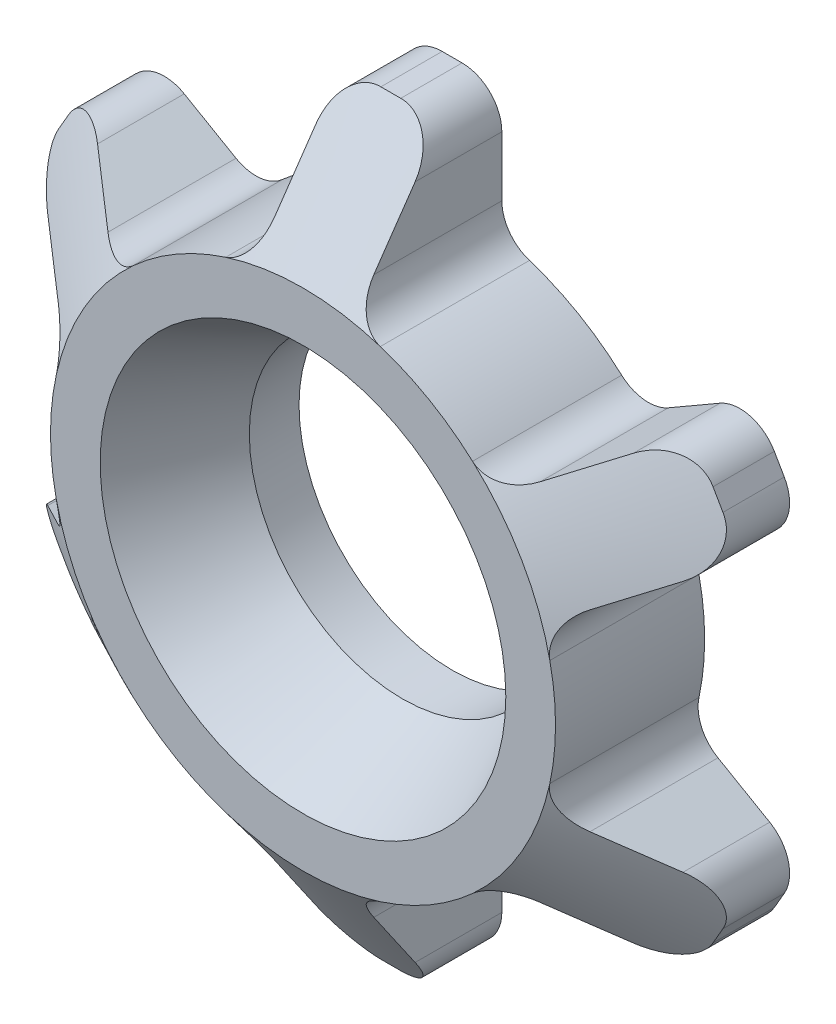
SolidWorks part; units mm, degrees
ref_plane "Front Plane" through (0, 0, 0) normal (0, 0, 1) x (1, 0, 0)
ref_plane "Top Plane" through (0, 0, 0) normal (0, 1, 0) x (1, 0, 0)
ref_plane "Right Plane" through (0, 0, 0) normal (1, 0, 0) x (0, 0, -1)
ref_axis "Axis1" through (0, 0, -0.7711) along (0, 0, 1)
sketch "Sketch1" plane through (0, 0, 0) normal (0, 0, 1) x (1, 0, 0)
  line L0 (0, 0) -> (0, 24.13)
  line L1 (-3.175, 24.13) -> (3.175, 24.13)
  line L2 (3.175, 24.13) -> (3.175, 15.8134)
  line L3 (-3.175, 24.13) -> (-3.175, 15.8134)
  circle A0 centre (0, 0) radius 9.779
  circle A1 centre (0, 0) radius 16.129
  point P9 (0, 24.13)
  dimension "D1" = 19.558
  dimension "D2" = 6.35
  dimension "D3" = 24.13
  dimension "D4" = 6.35
extrude "Boss-Extrude1" add sketch "Sketch1" along normal blind 9.525 contours A1 A0 | A1 L0 L1 L3 | A1 L2 L1 L0 region at (1.5502, 15.5959, 0) region at (-1.5978, 20.0766, 0) region at (1.5978, 20.0766, 0)
pattern_circular "CirPattern1" count 6 over 360 about axis through (0, 0, -0.7711) along (0, 0, 1) of "Boss-Extrude1" reverse direction yes
sketch "Sketch4" plane through (0, 0, 0) normal (0, 1, 0) x (1, 0, 0)
  line L2 (16.129, -9.525) -> (26.289, -2.4109)
  line L3 (16.129, 0) -> (26.289, 0)
  line L4 (26.289, 0) -> (26.289, -2.4109)
  line L5 (16.129, -9.525) -> (16.129, -13.1398)
  line L6 (16.129, -13.1398) -> (32.4273, -13.1398)
  line L7 (32.4273, -13.1398) -> (32.4273, 0)
  line L8 (32.4273, 0) -> (26.289, 0)
  line L9 (16.129, 0) -> (16.129, -9.525)
  line L10 (16.129, 0) -> (16.129, -9.525)
  dimension "D1" = 10.16
  dimension "D2" = 35
revolve "Cut-Revolve2" cut sketch "Sketch4" angle 360 about axis through (0, 0, -0.7711) along (0, 0, 1) region at (25.889, 0, 7.8466)
chamfer "Chamfer1" distance 3.175 distance2 6.35 1 edges at (9.779, 0, 9.525) first distance on face at (9.779, 0, 9.525)
fillet "Fillet1" radius 2.54 24 edges at (-12.1073, 10.6563, 4.7625) (-19.3097, 14.8146, 1.8885) (-22.4847, 9.3154, 1.8885) (-15.2823, 5.1571, 4.7625) (-15.2823, -5.1571, 4.7625) (-22.4847, -9.3154, 1.8885) (-19.3097, -14.8146, 1.8885) (-12.1073, -10.6563, 4.7625) (-3.175, -24.13, 1.8885) (3.175, -24.13, 1.8885) (19.3097, -14.8146, 1.8885) (22.4847, -9.3154, 1.8885) (15.2823, -5.1571, 4.7625) (15.2823, 5.1571, 4.7625) (22.4847, 9.3154, 1.8885) (19.3097, 14.8146, 1.8885) (12.1073, 10.6563, 4.7625) (3.175, 15.8134, 4.7625) (3.175, 24.13, 1.8885) (-3.175, 24.13, 1.8885) (-3.175, 15.8134, 4.7625) (-3.175, -15.8134, 4.7625) (3.175, -15.8134, 4.7625) (12.1073, -10.6563, 4.7625)
